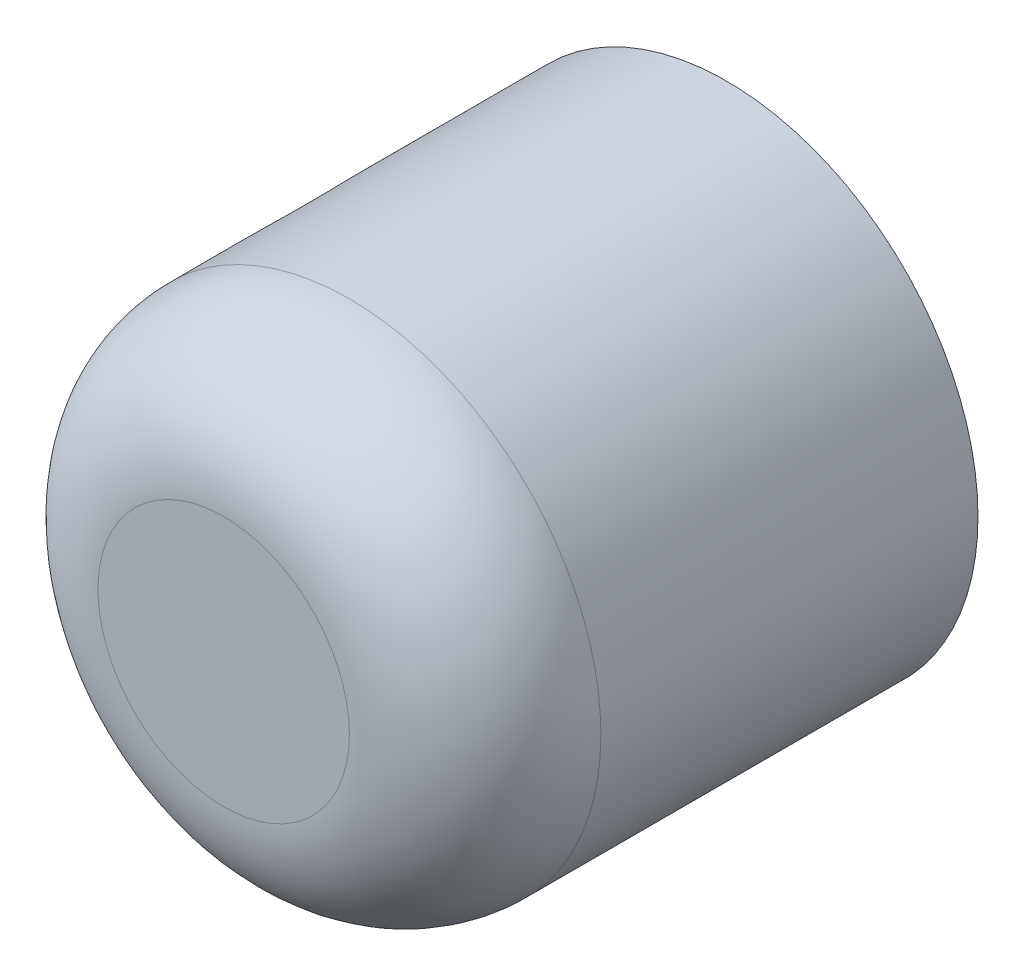
SolidWorks part; units mm, degrees
material "Hexcel AS4C (3000 Filaments)"
ref_plane "Front Plane" through (0, 0, 0) normal (0, 0, 1) x (1, 0, 0)
ref_plane "Top Plane" through (0, 0, 0) normal (0, 1, 0) x (1, 0, 0)
ref_plane "Right Plane" through (0, 0, 0) normal (1, 0, 0) x (0, 0, -1)
sketch "Sketch1" plane through (0, 0, 0) normal (0, 0, 1) x (1, 0, 0)
  circle A0 centre (0, 0) radius 20
  dimension "D1" = 40
extrude "Boss-Extrude1" add sketch "Sketch1" along normal blind 40
ref_plane "Plane1" through (-20, 0, 0) normal (-1, 0, 0) x (0, 0, 1)
sketch "Sketch2" plane through (-20, 0, 0) normal (-1, 0, 0) x (0, 0, 1)
  line L0 (0, 0) -> (40, 0) construction
  line L1 (40, -20) -> (40, 20) construction
  line L2 (20, 20) -> (20, -20) construction
  line L3 (40, 20) -> (0, 20) construction
  line L4 (0, -20) -> (40, -20) construction
  circle A1 centre (20, 0) radius 15
  dimension "D1" = 30
extrude "Cut-Extrude1" cut sketch "Sketch2" against normal blind 25
fillet "Fillet1" radius 10 1 edges at (20, 0, 40)
